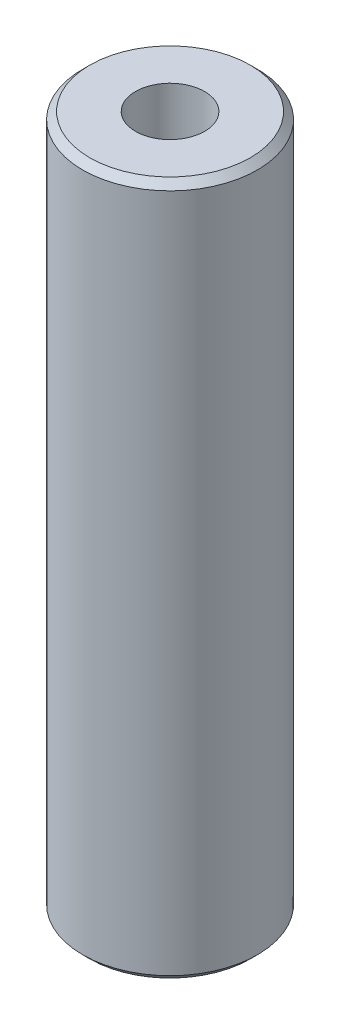
SolidWorks part; units mm, degrees
ref_plane "Front Plane" through (0, 0, 0) normal (0, 0, 1) x (1, 0, 0)
ref_plane "Top Plane" through (0, 0, 0) normal (0, 1, 0) x (1, 0, 0)
ref_plane "Right Plane" through (0, 0, 0) normal (1, 0, 0) x (0, 0, -1)
sketch "Sketch1" plane through (0, 0, 0) normal (0, 1, 0) x (1, 0, 0)
  circle A0 centre (0, 0) radius 42.5
  dimension "SHAFT_OD" = 85
extrude "Boss-Extrude1" add sketch "Sketch1" along normal blind 337.633
sketch "Sketch2" plane through (0, 0, 0) normal (0, 1, 0) x (1, 0, 0)
  circle A0 centre (0, 0) radius 16.822
  dimension "BORE_D" = 33.644
extrude "Cut-Extrude1" cut sketch "Sketch2" along normal through all
chamfer "Chamfer1" distance 3.4369 angle 45 2 edges at (0, 337.633, 42.5) (0, 0, 42.5)
